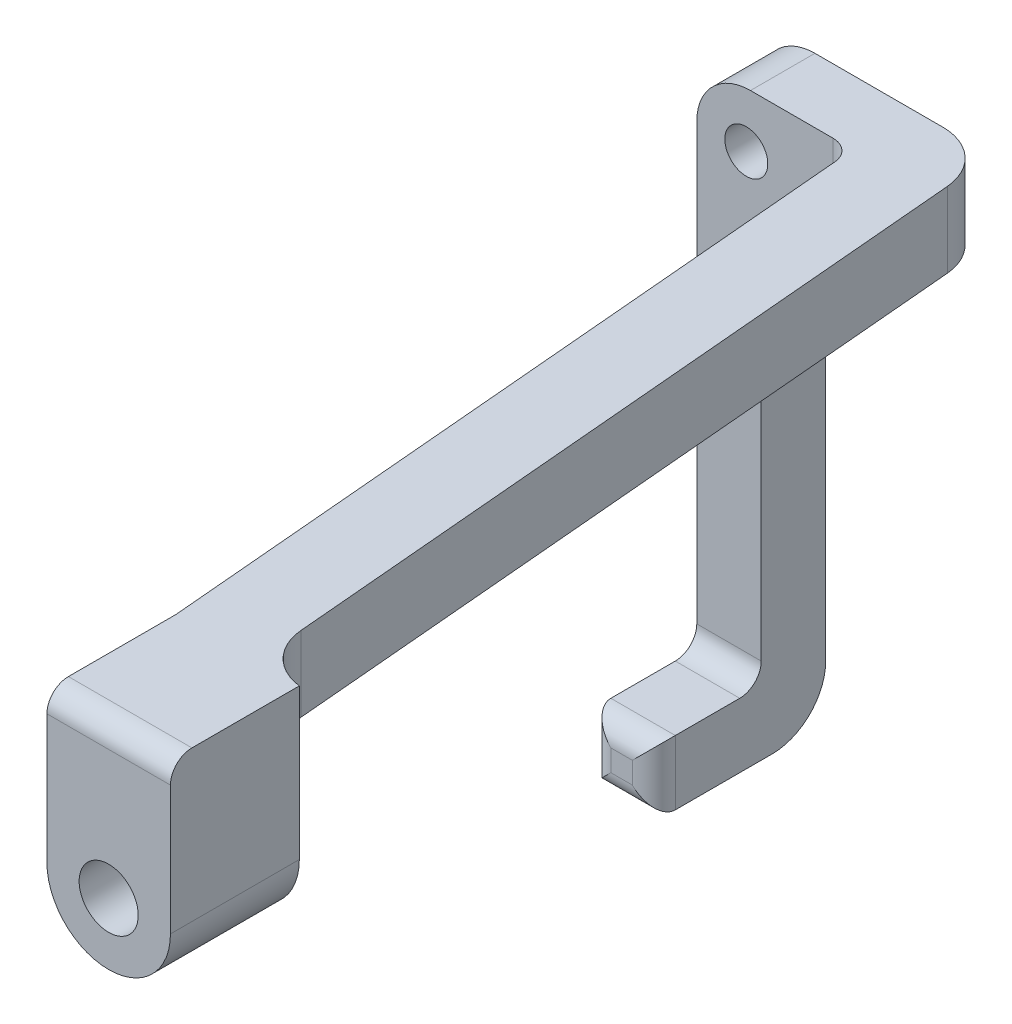
SolidWorks part; units mm, degrees
ref_plane "Front Plane" through (0, 0, 0) normal (1, 0, 0) x (0, 1, 0)
ref_plane "Top Plane" through (0, 0, 0) normal (0, 0, 1) x (0, 1, 0)
ref_plane "Right Plane" through (0, 0, 0) normal (0, 1, 0) x (-1, 0, 0)
sketch "Sketch1" plane through (0, 0, 0) normal (0, 0, 1) x (0, 1, 0)
  line L0 (0, 0) -> (1.375, 0) construction
  line L3 (0, 2.875) -> (7, 2.875)
  line L4 (0, -2.875) -> (7, -2.875)
  line L5 (7, -2.875) -> (7, 2.875)
  arc A0 (0, 2.875) -> (0, -2.875) centre (0, 0) ccw
  circle A3 centre (0, 0) radius 1.375
  point P2 (0, 0)
  dimension "D1" = 2.75
  dimension "D2" = 2.875
  dimension "D3" = 7
extrude "Boss-Extrude1" add sketch "Sketch1" along normal blind 6
sketch "Sketch2" plane through (0, 0, 0) normal (0, 0, -1) x (1, 0, 0)
  line L0 (2.875, -7) -> (-2.875, -7) construction
  line L1 (0.875, -7) -> (-2.875, -7)
  line L2 (2.875, 0) -> (2.875, -7) construction
  line L3 (-2.875, -7) -> (-2.875, 0) construction
  line L4 (0.875, -3.5) -> (0.875, -7)
  line L5 (-2.875, -7) -> (-2.875, -3.5)
  line L6 (-2.875, -3.5) -> (0.875, -3.5)
  dimension "D1" = 2
ref_plane "Plane1" through (0, 0, -37.5) normal (0, 0, -1) x (-1, 0, 0)
sketch "Sketch8" plane through (0, 0, -37.5) normal (0, 0, -1) x (-1, 0, 0)
  line L0 (-0.875, 3.5) -> (-0.875, 7) construction
  line L1 (2.875, 3.5) -> (-0.875, 3.5) construction
  line L2 (2.875, 7) -> (2.875, 3.5) construction
  line L3 (-0.875, 7) -> (2.875, 7) construction
  line L4 (-0.875, 3.5) -> (-0.875, 7) construction
  line L5 (2.875, 3.5) -> (-0.875, 3.5) construction
  line L6 (2.875, 7) -> (2.875, 3.5) construction
  line L7 (-0.875, 7) -> (2.875, 7) construction
  line L8 (2.375, 3.5) -> (2.375, 7)
  line L9 (6.125, 3.5) -> (6.125, 7)
  line L10 (2.375, 7) -> (6.125, 7)
  line L11 (6.125, 3.5) -> (2.375, 3.5)
  dimension "D1" = 3.25
loft "Loft1" add profiles "Sketch2", "Sketch8" connector at (0.875, 3.5, 0) connector at (-2.375, 3.5, -37.5)
sketch "Sketch9" plane through (0, 0, 0) normal (1, 0, 0) x (0, 1, 0)
  line L0 (3.5, 0) -> (3.5, -37.5) construction
  line L1 (7, 0) -> (7, -37.5) construction
  line L2 (3.5, -34.5) -> (3.5, -37.5)
  line L3 (7, -34.5) -> (7, -37.5)
  line L4 (7, -37.5) -> (3.5, -37.5)
  line L6 (7, -34.5) -> (3.5, -34.5)
  dimension "D1" = 3
extrude "Boss-Extrude2" add sketch "Sketch9" against normal blind 7 and the other way up to surface from vertex other way up to face at (-3.6875, 4.8125, -9.375) starting at point (-6.125, 7, -37.5)
sketch "Sketch10" plane through (0, 7, 0) normal (0, 1, 0) x (-1, 0, 0)
  line L0 (13.125, -37.5) -> (6.125, -37.5) construction
  line L1 (13.125, -37.5) -> (13.125, -34.5) construction
  line L2 (5.865, -34.5) -> (13.125, -34.5) construction
  line L3 (13.125, -37.5) -> (10.125, -37.5)
  line L4 (13.125, -37.5) -> (13.125, -34.5)
  line L5 (10.125, -34.5) -> (13.125, -34.5)
  line L6 (10.125, -34.5) -> (10.125, -37.5)
  dimension "D1" = 3
extrude "Boss-Extrude3" add sketch "Sketch10" against normal blind 23.25 from surface starting at face at (-5.6064, 3.5, -20.7857)
sketch "Sketch11" plane through (0, 0, -34.5) normal (0, 0, 1) x (1, 0, 0)
  line L0 (-13.125, -19.75) -> (-13.125, 7) construction
  line L2 (-10.125, -19.75) -> (-10.125, 3.5) construction
  line L3 (-13.125, -16.75) -> (-13.125, -19.75)
  line L4 (-13.125, -16.75) -> (-10.125, -16.75)
  line L5 (-10.125, -16.75) -> (-10.125, -19.75)
  line L6 (-10.125, -19.75) -> (-13.125, -19.75)
  line L7 (-13.125, -19.75) -> (-10.125, -19.75) construction
  dimension "D1" = 3
extrude "Boss-Extrude4" add sketch "Sketch11" along normal blind 5
fillet "Fillet1" radius 2.5 4 edges at (-11.625, -19.75, -37.5) (-13.125, 7, -36)
fillet "Fillet2" radius 1 7 edges at (-10.125, -18.25, -29.5) (-11.625, -19.75, -29.5) (-13.125, -18.25, -29.5) (-11.625, -16.75, -29.5) (0, 7, 6) (-5.865, 5.25, -34.5) (-11.625, -16.75, -34.5)
fillet "Fillet3" radius 3 1 edges at (-10.125, 3.5, -36)
sketch "Sketch12" plane through (0, 0, -37.5) normal (0, 0, -1) x (1, 0, 0)
  line L0 (-12.3928, -6.2678) -> (-9.2463, -2.6213) construction
  circle A0 centre (-10.8195, -4.4445) radius 1
  arc A1 (-13.125, -4.5) -> (-10.625, -7) centre (-10.625, -4.5) ccw construction
  arc A2 (-10.125, -0.5) -> (-7.125, -3.5) centre (-7.125, -0.5) ccw construction
  arc A3 (-13.125, -4.5) -> (-10.625, -7) centre (-10.625, -4.5) ccw construction
  arc A4 (-10.125, -0.5) -> (-7.125, -3.5) centre (-7.125, -0.5) ccw construction
  dimension "D1" = 2
extrude "Cut-Extrude1" cut sketch "Sketch12" against normal up to next
